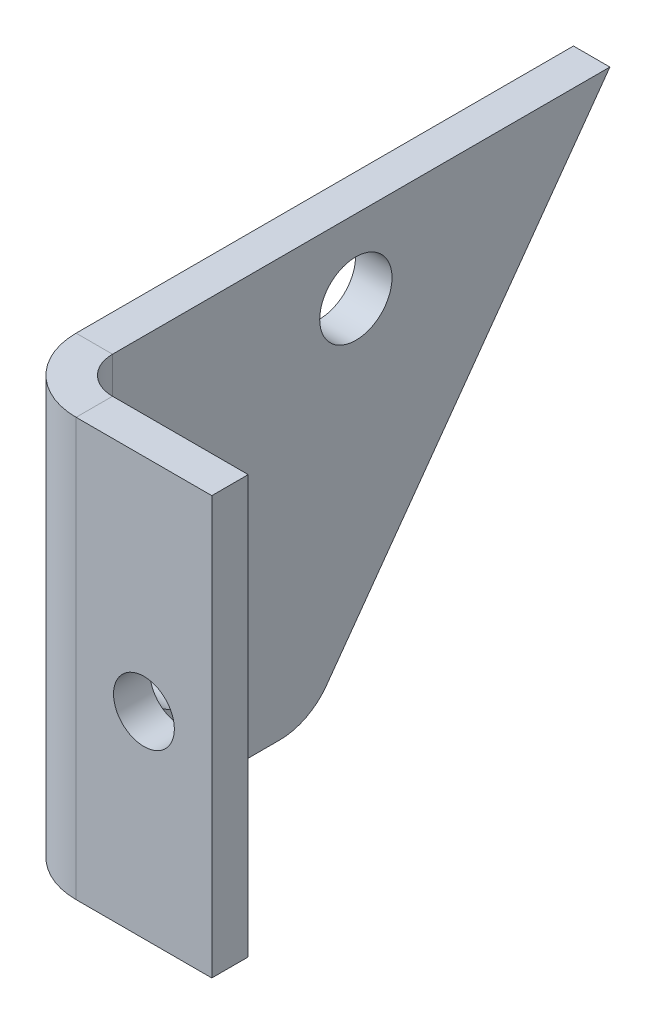
SolidWorks part; units mm, degrees
note: The reader was unsure of these and kept them because the rebuilt part matched: flange length of "Edge-Flange1".
ref_plane "Front Plane" through (0, 0, 0) normal (0, 0, 1) x (1, 0, 0)
ref_plane "Top Plane" through (0, 0, 0) normal (0, 1, 0) x (1, 0, 0)
ref_plane "Right Plane" through (0, 0, 0) normal (1, 0, 0) x (0, 0, -1)
sketch "Sketch1" plane through (0, 0, 0) normal (1, 0, 0) x (0, 0, -1)
  line B0 (15.5145, 80.4634) -> (48.2755, 80.6063)
  line B1 (53.2972, 75.6298) -> (53.4491, 43.2583)
  line B2 (0, 0) -> (0, 38.4283)
  line B3 (0, 38.4283) -> (-38.5, 38.5)
  line B4 (-38.5, 38.5) -> (-38.5, 49.4616)
  line B5 (-35.8424, 53.8789) -> (13.1939, 79.8808)
  line B6 (0, 0) -> (20.9311, 0)
  line B7 (24.9893, 2.0792) -> (52.5074, 40.3141)
  arc B8 (53.2972, 75.6298) -> (48.2755, 80.6063) centre (48.2973, 75.6063) ccw
  arc B9 (-38.5, 49.4616) -> (-35.8424, 53.8789) centre (-33.5, 49.4616) cw
  arc B10 (20.9311, 0) -> (24.9893, 2.0792) centre (20.9311, 5) ccw
  circle B11 centre (16.9387, 43.9655) radius 1.5
  ellipse B12 centre (47.9374, 44.1038) end of major axis (47.1974, 45.4086) minor radius 1.5
  spline B13 degree 3 poles (27.4588, 48.3261) (32.0962, 47.4253) (36.7252, 48.3676) (40.6413, 51.0097) (43.2482, 54.9493) (44.149, 59.5866) (43.2066, 64.2157) (40.5646, 68.1317) (36.625, 70.7386) (31.9877, 71.6394) (27.3586, 70.6971) (23.4426, 68.055) (20.8357, 64.1154) (19.9348, 59.4781) (20.8772, 54.8491) (23.5193, 50.933) (27.4588, 48.3261) (32.0962, 47.4253) (36.7252, 48.3676) knots -1.178097 -0.785398 -0.392699 0 0.392699 0.785398 1.178097 1.570796 1.963495 2.356194 2.748894 3.141593 3.534292 3.926991 4.31969 4.712389 5.105088 5.497787 5.890486 6.283185 6.675884 7.068583 7.461283 only from (32.0948, 47.7325) to (32.0948, 47.7325)
sketch_block_instance "motormount-1"
sketch_block "motormount" parameters "D1"=5
sketch "Sketch2" plane through (0, 0, 0) normal (1, 0, 0) x (0, 0, -1)
  line L0 (0, 0) -> (0, 38.4283) construction
  line L1 (0, 0) -> (20.9311, 0) construction
  line L2 (24.9893, 2.0792) -> (52.5074, 40.3141) construction
  line L3 (0, 0) -> (0, 36.404)
  line L4 (0, 0) -> (20.9311, 0)
  line L5 (24.9893, 2.0792) -> (49.6932, 36.404)
  line L6 (0, 36.404) -> (49.6932, 36.404)
  arc A0 (20.9311, 0) -> (24.9893, 2.0792) centre (20.9311, 5) ccw construction
  arc A1 (20.9311, 0) -> (24.9893, 2.0792) centre (20.9311, 5) ccw
base flange "Base-Flange1" sketch "Sketch2" thickness 3.175 reverse thickness direction no parameters "D1"=3.175
sketch "Sketch7" plane through (-3.175, 0, 0) normal (-1, 0, 0) x (0, 0, 1)
  line L0 (0, 0) -> (0, 10) construction
  line L1 (0, 0) -> (0, 38.4283) construction
  line L2 (-12.5877, 6.85) -> (-12.5877, 13.15) construction
  line L3 (0, 10) -> (0, 30.7947) construction
  line L4 (-26.1531, 27.1786) -> (-28.9547, 32.8214) construction
  line L5 (0, 10) -> (-30.69, 10)
  line L6 (-24.9893, 2.0792) -> (-52.5074, 40.3141) construction
  line L10 (-24.9893, 2.0792) -> (-49.6932, 36.404) construction
  line L11 (-24.9893, 2.0792) -> (-49.6932, 36.404)
  circle A0 centre (-27.5539, 30) radius 3.15
  circle A1 centre (-12.5877, 10) radius 3.15
  point P9 (-12.5877, 10)
  point P15 (-22.5421, 30)
  dimension "D3" = 6.3
  dimension "D4" = 6.3
  dimension "D1" = 10
  dimension "D2" = 20
extrude "Cut-Extrude3" cut sketch "Sketch7" against normal blind 10 contours A0 | A1 normal cut yes
edge flange "Edge-Flange1" sketch "Sketch11" flange angle 90 flange length 15 flange position material inside bend radius 3.175 thickness 3.175 relief rectangular parameters "D6"=10
sketch "Sketch11" plane through (0, 0, 0) normal (0, 0, -1) x (0, 1, 0)
  line L0 (36.404, 0) -> (0, 0) construction
  line L2 (0, 0) -> (0, 15)
  line L3 (0, 15) -> (36.404, 15)
  line L4 (36.404, 15) -> (36.404, 0)
  line L5 (36.404, 0) -> (0, 0)
bend "EdgeBend1" bend radius 3.175 bend angle 90 parameters "D5"=1
sketch "Sketch12" plane through (0, 0, -3.175) normal (0, 0, -1) x (-1, 0, 0)
  line L0 (-9.0875, 36.404) -> (-9.0875, -2.0794) construction
  line L1 (-3.175, 36.404) -> (-15, 36.404) construction
  circle A0 centre (-9.0875, 17.1623) radius 2.65
  point P6 (0, 0)
  point P7 (-9.0875, 17.1623)
  line B0 (-29.9965, 69.0289) -> (-29.9971, 63.0289)
  line B1 (-29.9971, 63.0289) -> (-9.9971, 63.0266)
  line B2 (-9.9971, 63.0266) -> (-9.9965, 69.0266)
  line B3 (-9.9965, 69.0266) -> (-29.9965, 69.0289)
  line B4 (-40.001, 30.03) -> (-40.0013, 27.03)
  line B5 (-40.0013, 27.03) -> (-30.0013, 27.0289)
  line B6 (-30.0013, 27.0289) -> (-30.001, 30.0289)
  line B7 (-10.0013, 27.0266) -> (-0.0013, 27.0254)
  line B8 (-0.0013, 27.0254) -> (-0.001, 30.0254)
  line B9 (-10.001, 30.0266) -> (-10.0013, 27.0266)
  line B10 (-30.0006, 33.0289) -> (-30.0013, 27.0289)
  line B11 (-30.0013, 27.0289) -> (-10.0013, 27.0266)
  line B12 (-10.0013, 27.0266) -> (-10.0006, 33.0266)
  line B13 (-0.001, 30.0254) -> (0.0032, 66.0254)
  line B14 (-9.9968, 66.0266) -> (-9.9971, 63.0266)
  line B15 (-9.9971, 63.0266) -> (-29.9971, 63.0289)
  line B16 (-29.9971, 63.0289) -> (-29.9968, 66.0289)
  line B17 (-39.9968, 66.03) -> (-40.001, 30.03)
  line B18 (-30.001, 30.0289) -> (-30.0006, 33.0289)
  line B19 (-10.0006, 33.0266) -> (-10.001, 30.0266)
  line B20 (-29.9965, 69.0289) -> (-39.9965, 69.03)
  line B21 (-39.9965, 69.03) -> (-39.9968, 66.03)
  line B22 (-29.9968, 66.0289) -> (-29.9965, 69.0289)
  line B23 (0.0032, 66.0254) -> (0.0035, 69.0254)
  line B24 (0.0035, 69.0254) -> (-9.9965, 69.0266)
  line B25 (-9.9965, 69.0266) -> (-9.9968, 66.0266)
  line B26 (380.7213, 17.1172) -> (-19.2787, 17.1635)
  line B27 (380.719, -2.8826) -> (-19.281, -2.8363)
  line B28 (380.718, -11.4112) -> (-19.282, -11.3649)
  line B29 (380.7223, 25.5884) -> (-19.2777, 25.6347)
  dimension "D1" = 5.3
sketch_block_instance "motormount_back-1"
sketch_block "motormount_back" parameters "D1"=5.4262, "D2"=5.7071
extrude "Cut-Extrude4" cut sketch "Sketch12" against normal blind 10 contours L0 A0 B26 | A0 L0 B26
sketch "Bend-Lines1" [suppressed] plane through (0, 0, 0) normal (0, 1, 0) x (1, 0, 0)
sketch "Bounding-Box1" [suppressed] plane through (0, 0, 0) normal (0, 1, 0) x (1, 0, 0)
sheet metal parameters "Sheet-Metal1" thickness 3.175 parameters "D1"=3.175
flat pattern "Flat-Pattern1" [suppressed]
sketch "Bend-Lines2" plane through (0, 0, 0) normal (0, 1, 0) x (1, 0, 0)
sketch3d "Bounding-Box2" [suppressed]
  line L0 (-20.9311, -5, 0) -> (28.7622, -5, 0) construction
  line L1 (-20.9311, 31.404, 0) -> (28.7622, 31.404, 0) construction
  line L2 (-20.9311, -5, 0) -> (-20.9311, 31.404, 0) construction
  line L3 (28.7622, -5, 0) -> (28.7622, 31.404, 0) construction
sketch "Sketch7-1" [suppressed] plane through (-3.175, 0, 0) normal (-1, 0, 0) x (0, 0, 1)
  line L0 (0, 0) -> (0, 9.9338) construction
  line L2 (-12.54, 6.7838) -> (-12.54, 13.0838) construction
  line L3 (0, 9.9338) -> (0, 30.7947) construction
  line L4 (-26.1531, 27.9733) -> (-28.9547, 33.6161) construction
  line L5 (0, 9.9338) -> (-30.6423, 9.9338)
  line L7 (0, 30.7947) -> (-45.6562, 30.7947)
  line L9 (-12.54, 9.9338) -> (-32.2907, 37.3762)
  line L11 (-24.9893, 2.0792) -> (-49.6932, 36.404)
  circle A0 centre (-27.5539, 30.7947) radius 3.15
  circle A1 centre (-12.54, 9.9338) radius 3.15
  point P9 (-12.54, 9.9338)
  point P15 (-22.5421, 30)
sheet metal parameters "Sheet-Metal4" thickness 3.175 parameters "D1"=3.175
flat pattern "Flat-Pattern1" [suppressed]
sketch "Bend-Lines2" plane through (0, 0, 0) normal (0, 1, 0) x (1, 0, 0)
sketch3d "Bounding-Box2" [suppressed]
  line L0 (-20.9311, -5, 0) -> (28.7622, -5, 0) construction
  line L1 (-20.9311, 31.404, 0) -> (28.7622, 31.404, 0) construction
  line L2 (-20.9311, -5, 0) -> (-20.9311, 31.404, 0) construction
  line L3 (28.7622, -5, 0) -> (28.7622, 31.404, 0) construction
sketch "Sketch7-1" [suppressed] plane through (-3.175, 0, 0) normal (-1, 0, 0) x (0, 0, 1)
  line L0 (0, 0) -> (0, 10) construction
  line L2 (-12.5877, 6.85) -> (-12.5877, 13.15) construction
  line L3 (0, 10) -> (0, 30.7947) construction
  line L4 (-26.1531, 27.1786) -> (-28.9547, 32.8214) construction
  line L5 (0, 10) -> (-30.69, 10)
  line L11 (-24.9893, 2.0792) -> (-49.6932, 36.404)
  circle A0 centre (-27.5539, 30) radius 3.15
  circle A1 centre (-12.5877, 10) radius 3.15
  point P9 (-12.5877, 10)
  point P15 (-22.5421, 30)
  dimension "D1" = 10
  dimension "D2" = 20
sheet metal parameters "Sheet-Metal5" thickness 3.175 parameters "D1"=3.175
flat pattern "Flat-Pattern1"
sketch "Bend-Lines2" plane through (0, 0, 0) normal (1, 0, 0) x (0, 0, -1)
  line L0 (2.7592, 36.404) -> (2.7592, 0) construction
  line L1 (2.7592, 36.404) -> (2.7592, 0) construction
sketch3d "Bounding-Box2" [suppressed]
  line L0 (-33.5878, -5, 0) -> (28.7622, -5, 0) construction
  line L1 (-33.5878, 31.404, 0) -> (28.7622, 31.404, 0) construction
  line L2 (-33.5878, -5, 0) -> (-33.5878, 31.404, 0) construction
  line L3 (28.7622, -5, 0) -> (28.7622, 31.404, 0) construction
bend of the flat pattern "Flatten-<EdgeBend1>1"
sheet metal parameters "Sheet-Metal6" thickness 3.175 parameters "D1"=3.175
flat pattern "Flat-Pattern1"
sketch "Bend-Lines2" plane through (0, 0, 0) normal (1, 0, 0) x (0, 0, -1)
  line L0 (2.7592, 36.404) -> (2.7592, 0) construction
  line L1 (2.7592, 36.404) -> (2.7592, 0) construction
sketch3d "Bounding-Box2" [suppressed]
  line L0 (-33.5878, -5, 0) -> (28.7622, -5, 0) construction
  line L1 (-33.5878, 31.404, 0) -> (28.7622, 31.404, 0) construction
  line L2 (-33.5878, -5, 0) -> (-33.5878, 31.404, 0) construction
  line L3 (28.7622, -5, 0) -> (28.7622, 31.404, 0) construction
bend of the flat pattern "Flatten-<EdgeBend1>1"
